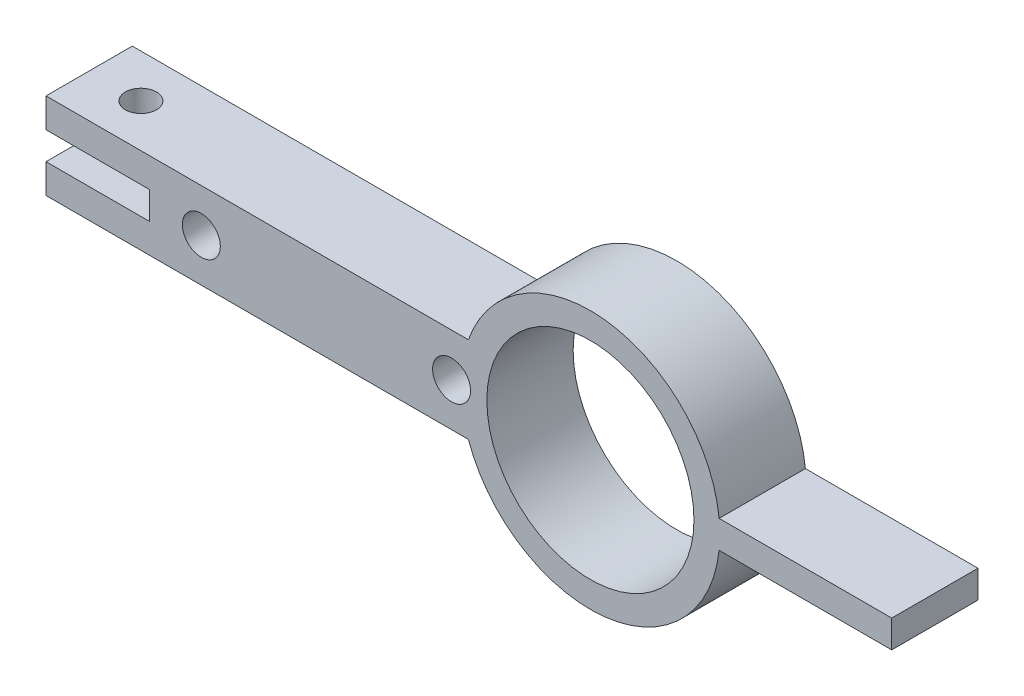
SolidWorks part; units mm, degrees
ref_plane "Front Plane" through (0, 0, 0) normal (0, 0, 1) x (1, 0, 0)
ref_plane "Top Plane" through (0, 0, 0) normal (0, 1, 0) x (1, 0, 0)
ref_plane "Right Plane" through (0, 0, 0) normal (1, 0, 0) x (0, 0, -1)
sketch "Sketch1" plane through (0, 0, 0) normal (0, 0, 1) x (1, 0, 0)
  line L0 (-31.5428, 2.5) -> (-7.0711, 2.5)
  line L1 (-31.5428, -2.5) -> (-7.0711, -2.5)
  line L2 (7.4572, 0.8) -> (17.4572, 0.8)
  line L3 (7.4572, -0.8) -> (17.4572, -0.8)
  line L4 (-31.5428, 2.5) -> (-31.5428, 0.8)
  line L5 (17.4572, 0.8) -> (17.4572, -0.8)
  line L6 (-7.5, 0) -> (7.5, 0) construction
  line L7 (-31.5428, 0.8) -> (-25.5428, 0.8)
  line L8 (-25.5428, 0.8) -> (-25.5428, -0.8)
  line L9 (-25.5428, -0.8) -> (-31.5428, -0.8)
  line L10 (-31.5428, -0.8) -> (-31.5428, -2.5)
  line L11 (-7.0711, 2.5) -> (-7.0711, -2.5) construction
  arc A0 (-7.0711, -2.5) -> (7.4572, -0.8) centre (0, 0) ccw
  arc A1 (7.4572, 0.8) -> (-7.0711, 2.5) centre (0, 0) ccw
  point P12 (-7.0711, 0)
  point P18 (17.4572, 0)
  dimension "D1" = 7.5
  dimension "D2" = 5
  dimension "D3" = 49
  dimension "D4" = 1.6
  dimension "D5" = 6
  dimension "D6" = 10
extrude "Boss-Extrude1" add sketch "Sketch1" along normal mid plane 5
hole_wizard "Tap Drill for M12x1.5 Tap1" positions "Sketch2" profile "Sketch3" hole size "M12x1.5" standard "ISO" end condition through all
sketch "Sketch2" plane through (0, 0, 2.5) normal (0, 0, 1) x (1, 0, 0)
  point P0 (0, 0)
sketch "Sketch3" plane through (0, 0, 2.5) normal (1, 0, 0) x (0, -1, 0)
  line L0 (0, 0) -> (0, 5)
  line L1 (0, 5) -> (6, 5)
  line L2 (6, 5) -> (6, 0)
  line L5 (6, 0) -> (0, 0)
  line L11 (0, -6.35) -> (0, 107.95) construction
  dimension "Thru Hole Dia." = 12
  dimension "Thru Hole Depth" = 5
sketch "Sketch4" plane through (0, 2.5, 0) normal (0, 1, 0) x (1, 0, 0)
  line L0 (-31.5428, -2.5) -> (-25.5428, -2.5) construction
  line L1 (-31.5428, -2.5) -> (-31.5428, 2.5) construction
  point P0 (-28.5428, 0)
  point P3 (-28.5428, -2.5)
  point P6 (-31.5428, 0)
hole_wizard "Hole1" positions "Sketch5" profile "Sketch6" legacy end condition through all
sketch "Sketch5" plane through (0, 2.5, 0) normal (0, 1, 0) x (1, 0, 0)
  point P0 (-28.5428, 0)
sketch "Sketch6" plane through (-28.5428, 2.5, 0) normal (1, 0, 0) x (0, 0, 1)
  line L0 (0, 0) -> (0, 10)
  line L1 (0, 10) -> (0.9, 10)
  line L2 (0.9, 10) -> (0.9, 0)
  line L3 (0.9, 0) -> (0, 0)
  line L4 (0, 110) -> (0, -10) construction
  dimension "Diameter" = 1.8
  dimension "Depth" = 10
sketch "Sketch7" plane through (0, 0, -2.5) normal (0, 0, 1) x (1, 0, 0)
  circle A0 centre (-8.0428, 0) radius 1.1 construction
  circle A1 centre (-22.5428, 0) radius 1.1 construction
  circle A2 centre (-8.0428, 0) radius 1.1
  circle A3 centre (-22.5428, 0) radius 1.1
extrude "Cut-Extrude1" cut sketch "Sketch7" along normal through all
